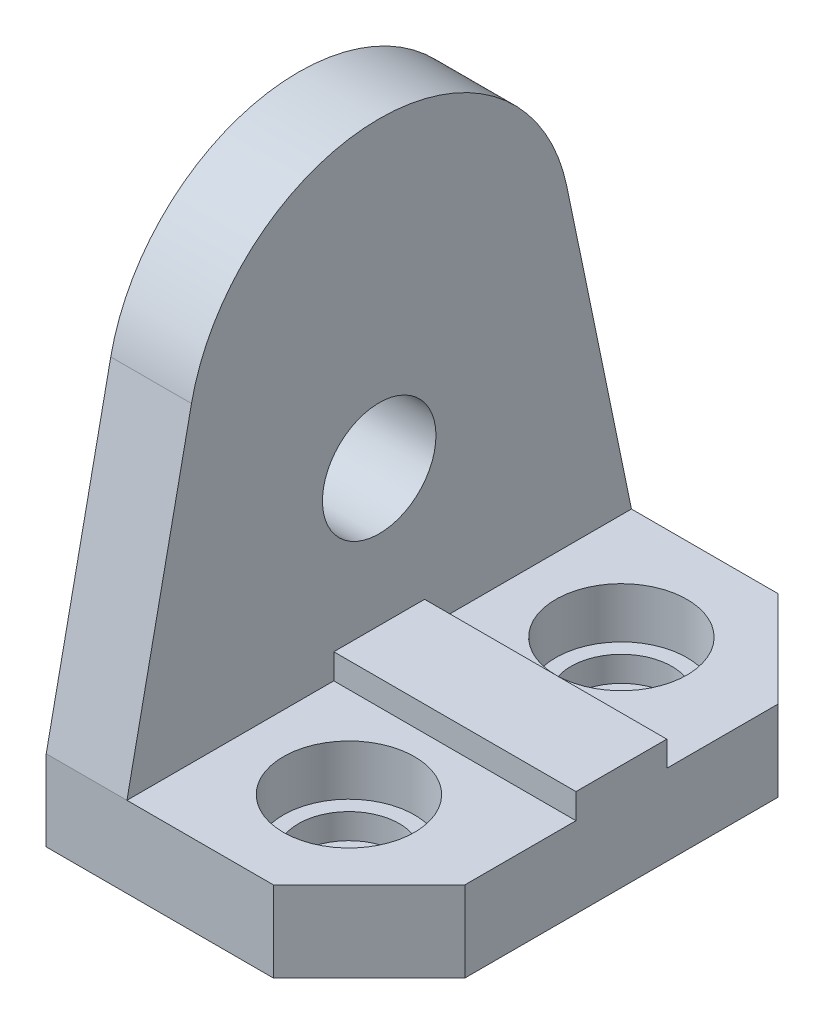
SolidWorks part; units mm, degrees
ref_plane "Front Plane" through (0, 0, 0) normal (0, 0, 1) x (1, 0, 0)
ref_plane "Top Plane" through (0, 0, 0) normal (0, 1, 0) x (1, 0, 0)
ref_plane "Right Plane" through (0, 0, 0) normal (1, 0, 0) x (0, 0, -1)
sketch "Sketch1" plane through (0, 0, 0) normal (0, 1, 0) x (1, 0, 0)
  line L0 (0, 0) -> (128, 0) construction
  line L1 (0, -100) -> (0, 100)
  line L2 (0, 100) -> (90, 100)
  line L3 (0, -100) -> (90, -100)
  line L4 (90, 100) -> (128, 62)
  line L5 (128, 62) -> (128, -62)
  line L6 (90, -100) -> (128, -62)
  line L7 (0, 0) -> (128, 0)
  line L8 (0, 0) -> (0, 18)
  line L9 (128, 0) -> (128, 18)
  line L10 (0, 18) -> (128, 18)
  line L11 (0, -18) -> (128, -18)
  point P10 (0, 0)
  point P12 (128, 18)
  point P13 (138.5471, 62)
  dimension "D5" = 18
  dimension "D1" = 128
  dimension "D2" = 124
  dimension "D3" = 38
  dimension "D4" = 90
extrude "Boss-Extrude1" add sketch "Sketch1" along normal blind 32 contours L11 L1 L3 L6 L5 | L1 L10 L5 L4 L2 region at (60.208, 0, 56.907) region at (60.208, 0, -56.907)
extrude "Boss-Extrude2" add sketch "Sketch1<3>" along normal blind 42 contours L10 L1 L7 L5 | L1 L11 L5 L7 region at (64, 0, 9) region at (64, 0, -9)
sketch "Sketch1<3>" plane through (0, 0, 0) normal (0, 1, 0) x (1, 0, 0) same geometry as "Sketch1"
sketch "Sketch2" plane through (0, 0, 0) normal (1, 0, 0) x (0, 0, -1)
  line L0 (-100, 32) -> (-74.4183, 155.4244)
  line L1 (74.4183, 155.4244) -> (100, 32)
  line L3 (62, 32) -> (18, 32) construction
  line L4 (-100, 32) -> (100, 32)
  arc A0 (-74.4183, 155.4244) -> (74.4183, 155.4244) centre (0, 140) cw
  circle A1 centre (0, 96) radius 22.5
  point P14 (21.5606, 32)
  dimension "D1" = 76
  dimension "D3" = 45
  dimension "D2" = 108
  dimension "D4" = 64
extrude "Boss-Extrude3" add sketch "Sketch2" along normal blind 32
sketch "Sketch4" plane through (0, 32, 0) normal (0, 1, 0) x (1, 0, 0)
  line L0 (32, -18) -> (128, -18) construction
  line L1 (32, 18) -> (128, 18) construction
  line L2 (32, 100) -> (32, 18) construction
  circle A0 centre (74, -54) radius 26
  circle A1 centre (74, -54) radius 20
  circle A2 centre (74, 54) radius 26
  circle A3 centre (74, 54) radius 20
  point P6 (0, 0)
  dimension "D1" = 52
  dimension "D2" = 40
  dimension "D3" = 52
  dimension "D4" = 40
  dimension "D5" = 36
  dimension "D6" = 36
  dimension "D7" = 42
extrude "Cut-Extrude1" cut sketch "Sketch4" against normal blind 20 contours A3 | A2 A3 | A0 A1 | A1 region at (48.7354, 32, 54) region at (74, 32, 54) region at (48.7354, 32, -54) region at (74, 32, -54)
extrude "Cut-Extrude2" cut sketch "Sketch4<3>" against normal blind 30 contours A3 | A1 region at (74, 32, 54) region at (74, 32, -54)
sketch "Sketch4<3>" plane through (0, 32, 0) normal (0, 1, 0) x (1, 0, 0) same geometry as "Sketch4"
